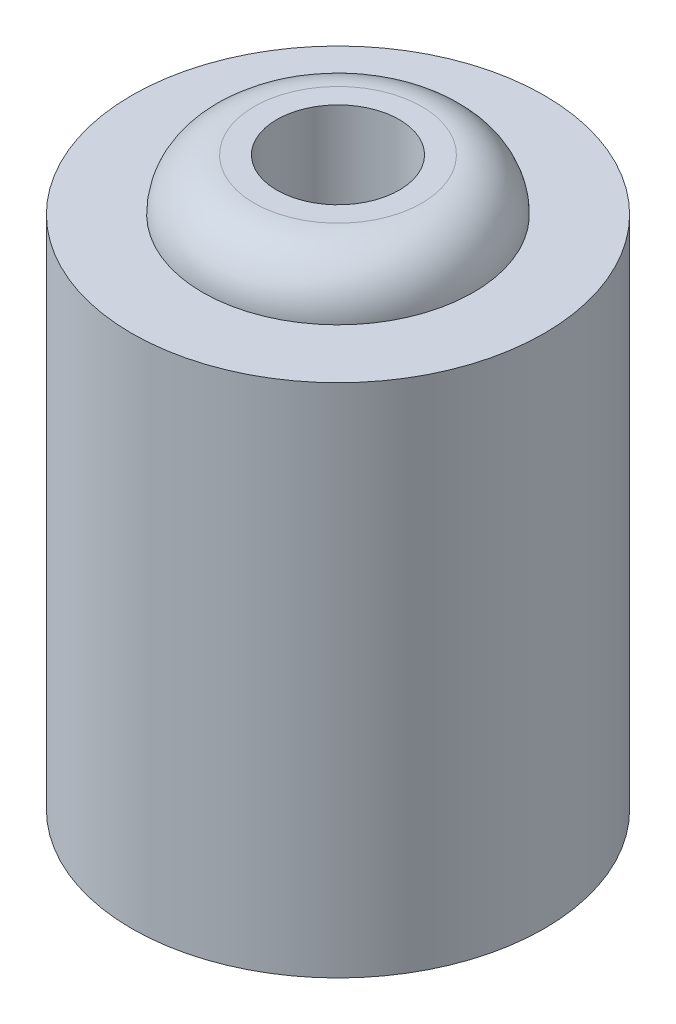
SolidWorks part; units mm, degrees
ref_plane "Front Plane" through (0, 0, 0) normal (0, 0, 1) x (1, 0, 0)
ref_plane "Top Plane" through (0, 0, 0) normal (0, 1, 0) x (1, 0, 0)
ref_plane "Right Plane" through (0, 0, 0) normal (1, 0, 0) x (0, 0, -1)
sketch "Sketch1" plane through (0, 0, 0) normal (0, 1, 0) x (1, 0, 0)
  circle A0 centre (0, 0) radius 8
  circle A1 centre (0, 0) radius 2.375
  dimension "D1" = 4.75
  dimension "D2" = 16
extrude "Boss-Extrude1" add sketch "Sketch1" along normal blind 20
sketch "Sketch2" plane through (0, 20, 0) normal (0, 1, 0) x (1, 0, 0)
  circle A0 centre (0, 0) radius 5.25
  circle A1 centre (0, 0) radius 2.375
  dimension "D1" = 10.5
  dimension "D2" = 4.75
extrude "Boss-Extrude2" add sketch "Sketch2" along normal blind 2
fillet "Fillet1" radius 2 1 edges at (0, 22, 5.25)
